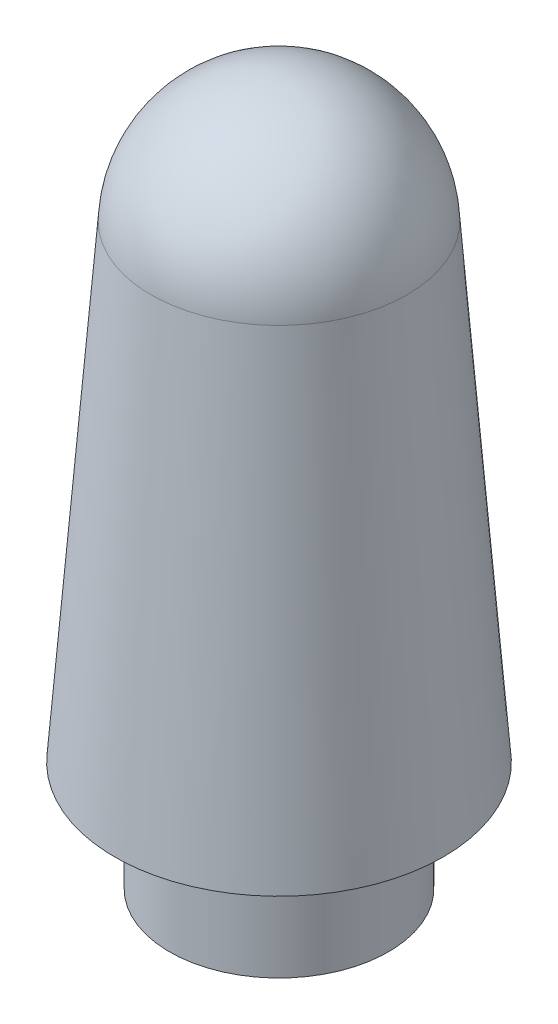
SolidWorks part; units mm, degrees
material "6061 Alloy"
ref_plane "Front Plane" through (0, 0, 0) normal (0, 0, 1) x (1, 0, 0)
ref_plane "Top Plane" through (0, 0, 0) normal (0, 1, 0) x (1, 0, 0)
ref_plane "Right Plane" through (0, 0, 0) normal (1, 0, 0) x (0, 0, -1)
sketch "Sketch2" plane through (0, 0, 0) normal (0, 0, 1) x (1, 0, 0)
  line L0 (0, 0) -> (12.7, 0)
  line L1 (12.7, 0) -> (12.7, 12.7)
  line L2 (12.7, 12.7) -> (19.05, 12.7)
  line L4 (0, 81.28) -> (0, 0)
  line L5 (14.8334, 67.0271) -> (19.05, 12.7)
  arc A0 (0, 81.28) -> (14.8334, 67.0271) centre (0, 66.4348) cw
  point P8 (12.7, 89.4464)
  point P9 (0, 0)
  point P10 (0, 0)
  point P11 (0, 0)
  point P12 (0, 0)
  point P13 (12.7, 51.1089)
  point P14 (0, 101.092)
  point P15 (13.9657, 46.0543)
  point P16 (13.9657, 56.423)
  point P17 (12.7, 62.1257)
  point P18 (17.2491, 50.893)
  point P19 (19.05, 27.9092)
  dimension "D1" = 12.7
  dimension "D2" = 12.7
  dimension "D3" = 19.05
  dimension "D4" = 81.28
revolve "Revolve1" add sketch "Sketch2" angle 360 about L4
sketch "Sketch3" plane through (0, 0, 0) normal (0, -1, 0) x (1, 0, 0)
  point P0 (0, 0)
hole_wizard "Tap Drill for 1/4-20 Tap1" positions "Sketch4" profile "Sketch6" hole size "1/4-20" standard "ANSI Inch"
sketch "Sketch4" plane through (0, 0, 0) normal (0, -1, 0) x (-1, 0, 0)
  point P0 (0, 0)
sketch "Sketch6" plane through (0, 0, 0) normal (1, 0, 0) x (0, 0, -1)
  line L0 (0, 0) -> (0, 26.67)
  line L1 (0, 26.67) -> (2.5527, 25.1362)
  line L2 (2.5527, 25.1362) -> (2.5527, 0)
  line L5 (2.5527, 0) -> (0, 0)
  line L10 (0, 26.67) -> (-2.5527, 25.1362) construction
  line L11 (0, -6.35) -> (0, 107.95) construction
  dimension "Hole Dia." = 5.1054
  dimension "Hole Depth" = 26.67
  dimension "Drill Angle" = 118
thread "Thread1" pitch 1.27 method extrude profile "Thread Profile1" start angle 0, offset 0, length 12.7, pitch 1.27, diameter 5.1054
ref_plane "Plane1" through (2.5527, 0, 0) normal (0, 0, 1) x (1, 0, 0)
sketch "Thread Profile1" plane through (2.5527, 0, 0) normal (0, 0, 1) x (1, 0, 0)
  line L0 (0, 0) -> (0, 1.27) construction
  line L11 (0, 0) -> (0, 1.1112)
  line L12 (0, 1.1112) -> (-0.6874, 0.7144)
  line L13 (-0.6874, 0.7144) -> (-0.6874, 0.3969)
  line L15 (-0.6874, 0.3969) -> (0, 0)
  line L17 (-0.6874, 0.5556) -> (0, 0.5556) construction
  point P2 (0, 0)
  dimension "Pitch" = 1.27
  dimension "Profile_Angle" = 60
  dimension "Profile_Land" = 0.3175
  dimension "Profile_Height" = 0.6874
